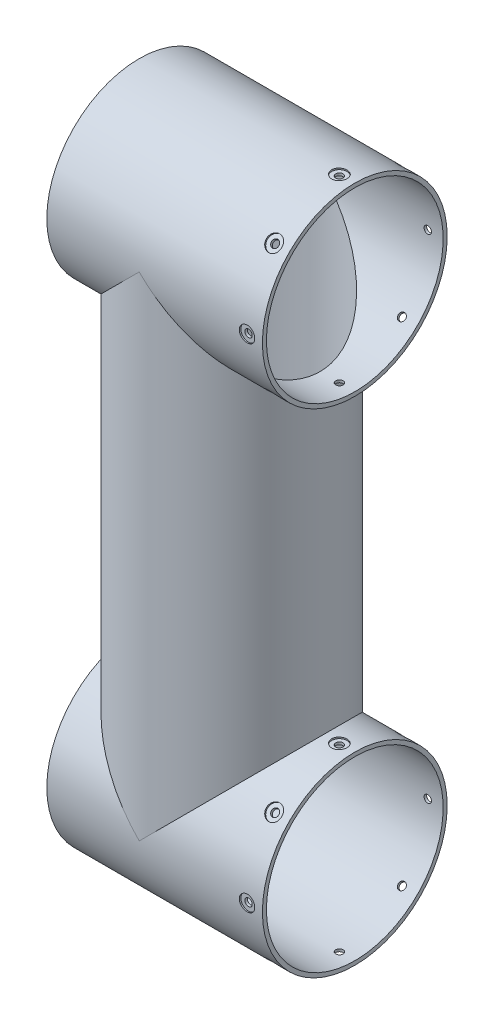
SolidWorks part; units mm, degrees
ref_plane "정면" through (0, 0, 0) normal (0, 0, 1) x (1, 0, 0)
ref_plane "윗면" through (0, 0, 0) normal (0, 1, 0) x (1, 0, 0)
ref_plane "우측면" through (0, 0, 0) normal (1, 0, 0) x (0, 0, -1)
sketch "스케치1" plane through (0, 0, 0) normal (0, 1, 0) x (1, 0, 0)
  circle A0 centre (0, 0) radius 30
  dimension "D1" = 60
extrude "보스-돌출1" add sketch "스케치1" along normal blind 160
sketch "스케치2" plane through (0, 0, 0) normal (1, 0, 0) x (0, 0, -1)
  line L0 (-30, 0) -> (30, 0) construction
  circle A0 centre (0, 0) radius 30
  dimension "D1" = 60
  dimension "D2" = 0
extrude "보스-돌출2" add sketch "스케치2" along normal blind 40 and the other way blind 30
sketch "스케치3" plane through (-30, 0, 0) normal (-1, 0, 0) x (0, 0, 1)
  circle A0 centre (0, 0) radius 28.7
  circle A1 centre (0, 0) radius 30 construction
  dimension "D1" = 1.3
extrude "컷-돌출1" cut sketch "스케치3" against normal through all
ref_plane "평면1" through (0, 80, 0) normal (0, 1, 0) x (1, 0, 0)
ref_plane "평면2" through (0, 0, -30) normal (0, 0, -1) x (-1, 0, 0)
sketch "스케치4" plane through (0, 160, 0) normal (0, 1, 0) x (1, 0, 0)
  circle A0 centre (0, 0) radius 28.7
  circle A1 centre (0, 0) radius 30 construction
  dimension "D1" = 1.3
sketch "스케치5" plane through (0, 0, -30) normal (0, 0, -1) x (-1, 0, 0)
  line L0 (-40, 30) -> (-40, -30) construction
  point P0 (-35, 0)
  dimension "D1" = 5
hole_wizard "M2 남비 머리 나사용 카운터보어1" positions "스케치6" profile "스케치7" counterbore size "M2" standard "ISO"
sketch "스케치6" plane through (0, 0, -30) normal (0, 0, -1) x (-1, 0, 0)
  point P0 (-35, 0)
sketch "스케치7" plane through (35, 0, -30) normal (1, 0, 0) x (0, 1, 0)
  line L0 (0, 0) -> (0, 10.721)
  line L1 (0, 10.721) -> (1.2, 10)
  line L2 (1.2, 10) -> (1.2, 0.5)
  line L3 (1.2, 0.5) -> (2.5, 0.5)
  line L4 (2.5, 0.5) -> (2.5, 0)
  line L5 (2.5, 0) -> (0, 0)
  line L10 (0, 10.721) -> (-1.2, 10) construction
  line L11 (0, -6.35) -> (0, 107.95) construction
  dimension "구멍 지름" = 2.4
  dimension "구멍 깊이" = 10
  dimension "카운터보어 지름" = 5
  dimension "카운터보어 깊이" = 0.5
  dimension "드릴 각도" = 118
pattern_circular "원형 패턴1" count 8 over 360 about axis through (40, 0, 0) along (1, 0, 0) of "M2 남비 머리 나사용 카운터보어1"
mirror "대칭 복사2" about plane through (0, 80, 0) normal (0, 1, 0) of "보스-돌출2", "컷-돌출1", "M2 남비 머리 나사용 카운터보어1", "원형 패턴1"
extrude "컷-돌출2" cut sketch "스케치4" against normal blind 160
